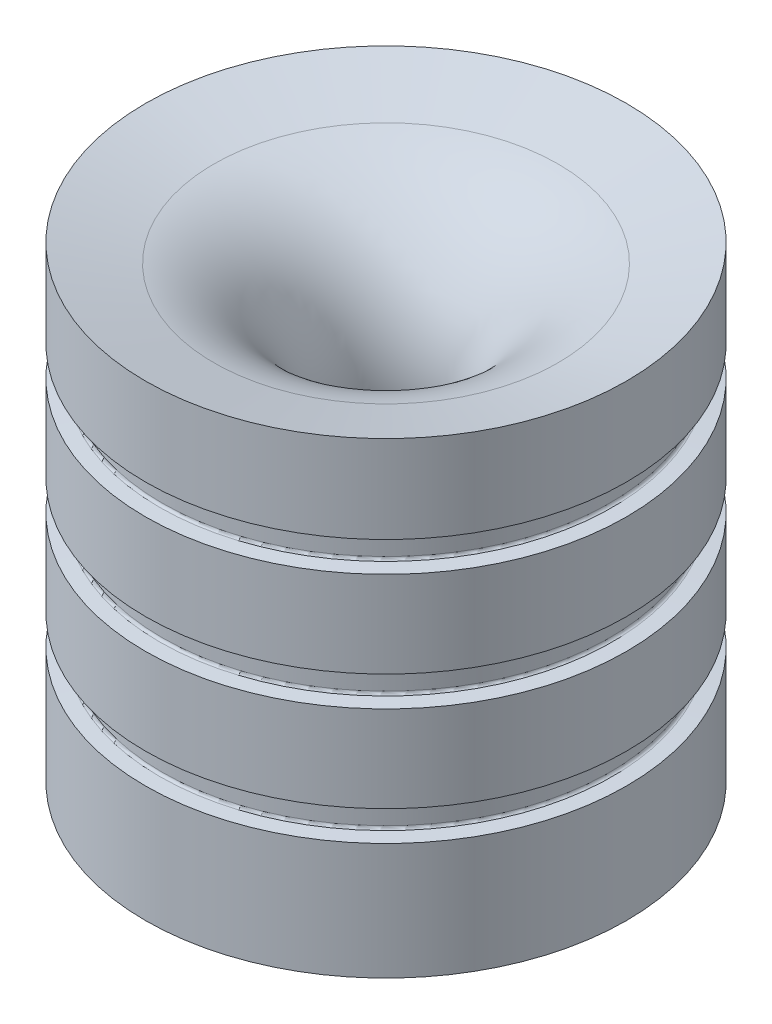
SolidWorks part; units mm, degrees
material "C (Graphite)"
ref_plane "Front Plane" through (0, 0, 0) normal (0, 0, 1) x (1, 0, 0)
ref_plane "Top Plane" through (0, 0, 0) normal (0, 1, 0) x (1, 0, 0)
ref_plane "Right Plane" through (0, 0, 0) normal (1, 0, 0) x (0, 0, -1)
sketch "Sketch1" plane through (0, 0, 0) normal (0, 0, 1) x (1, 0, 0)
  line L0 (0, -55) -> (0, 55) construction
  line L1 (41.275, 80.1867) -> (41.275, 0)
  line L2 (41.275, 80.1867) -> (29.5457, 77.0439)
  line L3 (41.275, 0) -> (23.2724, 0)
  line L4 (23.2724, 0) -> (11.1609, 45.2005)
  line L5 (0, 11.2039) -> (0, 47.7588) construction
  arc A0 (11.1609, 45.2005) -> (29.5457, 77.0439) centre (36.275, 51.9298) cw
  dimension "D6" = 36.275
  dimension "D3" = 26
  dimension "D1" = 41.275
  dimension "D2" = 23.2724
  dimension "D4" = 105
  dimension "D5" = 75
revolve "Revolve1" add sketch "Sketch1" angle 360 about L5
ref_plane "Plane1" through (0, 11.2039, 0) normal (-1, 0, 0) x (0, 0, -1)
sketch "Sketch3" plane through (0, 11.2039, 0) normal (-1, 0, 0) x (0, 0, -1)
  line L0 (38.8614, -9.0151) -> (41.3639, -8.7961)
  line L1 (41.3639, -8.7961) -> (41.3639, -13.9838)
  line L2 (41.3639, -13.9838) -> (38.8614, -13.7649)
  line L3 (38.4556, -13.322) -> (38.4556, -9.4579)
  line L4 (0, 50) -> (0, -50) construction
  line L5 (41.275, 11.2039) -> (-41.275, 11.2039) construction
  arc A0 (38.8614, -13.7649) -> (38.4556, -13.322) centre (38.9001, -13.322) cw
  arc A1 (38.4556, -9.4579) -> (38.8614, -9.0151) centre (38.9001, -9.4579) cw
  dimension "D1" = 20
revolve "Groove for AS 568-234, O-Ring1" cut sketch "Sketch3"
pattern_linear "LPattern1" count 3 spacing 20 along (0, 1, 0) of "Groove for AS 568-234, O-Ring1"
